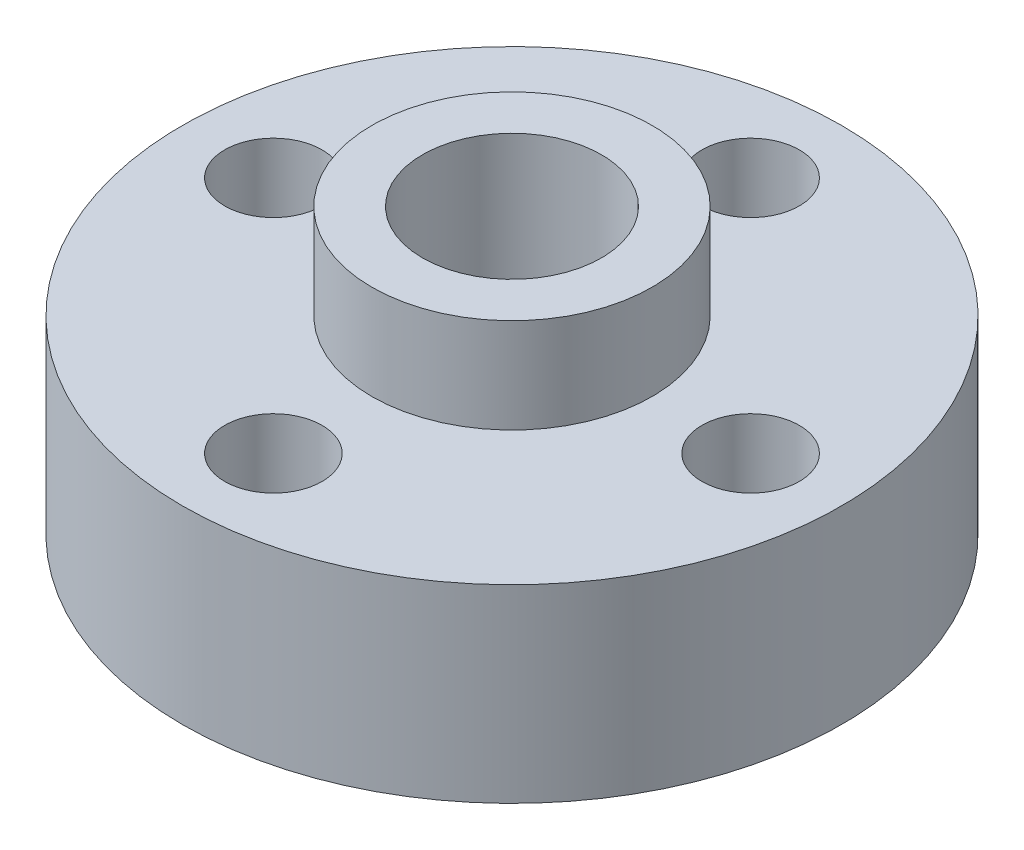
SolidWorks part; units mm, degrees
material "6061 Alloy"
ref_plane "Front Plane" through (0, 0, 0) normal (0, 0, 1) x (1, 0, 0)
ref_plane "Top Plane" through (0, 0, 0) normal (0, 1, 0) x (1, 0, 0)
ref_plane "Right Plane" through (0, 0, 0) normal (1, 0, 0) x (0, 0, -1)
sketch "Sketch1" plane through (0, 0, 0) normal (0, 1, 0) x (1, 0, 0)
  line L0 (0, 0) -> (0, 8) construction
  circle A0 centre (0, 0) radius 3
  circle A1 centre (0, 0) radius 4.699
  circle A2 centre (0, 0) radius 11.049
  circle A3 centre (0, 8) radius 1.6319
  circle A4 centre (8, 0) radius 1.632
  circle A5 centre (0, -8) radius 1.632
  circle A6 centre (-8, 0) radius 1.632
  point P15 (0, 0)
  dimension "D1" = 4
extrude "Boss-Extrude1" add sketch "Sketch1" along normal mid plane 12.7 contours A0 A1 region at (-4.5661, 0, 0)
extrude "Boss-Extrude2" add sketch "Sketch1<3>" along normal mid plane 6.35 contours A2 A6 A5 A4 A1 A3 region at (-10.7365, 0, 0)
sketch "Sketch1<3>" plane through (0, 0, 0) normal (0, 1, 0) x (1, 0, 0) same geometry as "Sketch1"
